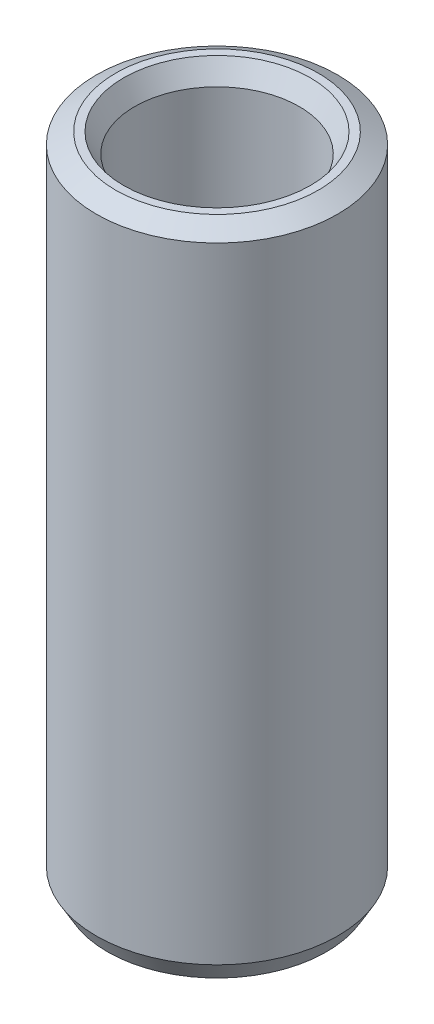
SolidWorks part; units mm, degrees
ref_plane "Front Plane" through (0, 0, 0) normal (0, 0, 1) x (1, 0, 0)
ref_plane "Top Plane" through (0, 0, 0) normal (0, 1, 0) x (1, 0, 0)
ref_plane "Right Plane" through (0, 0, 0) normal (1, 0, 0) x (0, 0, -1)
sketch "Sketch1" plane through (0, 0, 0) normal (0, 1, 0) x (1, 0, 0)
  circle A0 centre (0, 0) radius 35
  dimension "SLEEVE_OD" = 70
extrude "Boss-Extrude1" add sketch "Sketch1" along normal blind 190.1388
sketch "Sketch2" plane through (0, 0, 0) normal (0, 1, 0) x (1, 0, 0)
  circle A0 centre (0, 0) radius 23.8509
  dimension "BORE_D" = 47.7018
extrude "Cut-Extrude1" cut sketch "Sketch2" along normal through all
chamfer "Chamfer1" distance 3.2305 angle 60 4 edges at (0, 190.1388, 23.8509) (0, 0, 23.8509) (0, 0, 35) (0, 190.1388, 35) first distance on face at (0, 190.1388, 23.8509) first distance on face at (0, 0, 23.8509) first distance on face at (0, 190.1388, 35)
